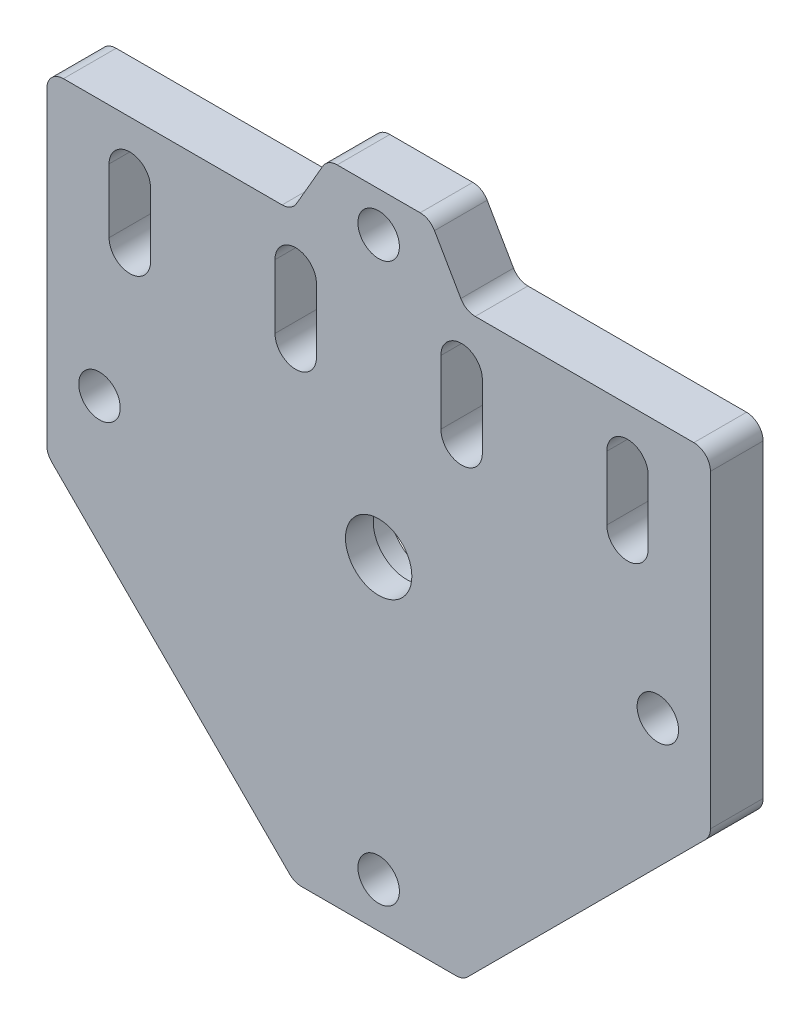
SolidWorks part; units mm, degrees
ref_plane "Front Plane" through (0, 0, 0) normal (0, 0, 1) x (1, 0, 0)
ref_plane "Top Plane" through (0, 0, 0) normal (0, 1, 0) x (1, 0, 0)
ref_plane "Right Plane" through (0, 0, 0) normal (1, 0, 0) x (0, 0, -1)
sketch "Sketch1" plane through (0, 0, 0) normal (0, 0, 1) x (1, 0, 0)
  line L0 (-23.6583, -20.95) -> (-30, -20.95) construction
  line L1 (-28, 10) -> (-1.6395, 10)
  line L2 (-30, 8) -> (-30, -29.3216)
  line L3 (0.6784, -60) -> (19.3216, -60)
  line L4 (50, 8) -> (50, -29.3216)
  line L5 (-5.36, 10) -> (5.36, 10) construction
  line L6 (43.6583, -20.95) -> (50, -20.95) construction
  line L7 (10, -20.95) -> (10, 10) construction
  line L8 (-23.6583, -20.95) -> (10, -20.95) construction
  line L9 (10, -54.6083) -> (10, -60) construction
  line L10 (-29.4142, -30.7358) -> (-0.7358, -59.4142)
  line L11 (20.7358, -59.4142) -> (49.4142, -30.7358)
  line L12 (0.0925, 11) -> (3.268, 16.5)
  line L13 (5, 17.5) -> (15, 17.5)
  line L14 (16.7321, 16.5) -> (19.9075, 11)
  line L15 (10, 10) -> (10, 17.5) construction
  line L17 (21.6395, 10) -> (48, 10)
  line L19 (10, -20.95) -> (43.6583, -20.95) construction
  line L20 (-49.855, -30.15) -> (-39.855, -30.15) construction
  line L21 (10, -54.6083) -> (10, -20.95) construction
  circle A0 centre (10, -20.95) radius 4
  circle A1 centre (43.6583, -20.95) radius 2.5
  circle A2 centre (10, -54.6083) radius 2.5
  circle A3 centre (-23.6583, -20.95) radius 2.5
  arc A4 (50, 8) -> (48, 10) centre (48, 8) ccw
  arc A5 (-28, 10) -> (-30, 8) centre (-28, 8) ccw
  circle A6 centre (10, 12.7083) radius 2.5
  arc A7 (-1.6395, 10) -> (0.0925, 11) centre (-1.6395, 12) ccw
  arc A8 (19.9075, 11) -> (21.6395, 10) centre (21.6395, 12) ccw
  arc A9 (16.7321, 16.5) -> (15, 17.5) centre (15, 15.5) ccw
  arc A10 (5, 17.5) -> (3.268, 16.5) centre (5, 15.5) ccw
  arc A11 (49.4142, -30.7358) -> (50, -29.3216) centre (48, -29.3216) ccw
  arc A12 (20.7358, -59.4142) -> (19.3216, -60) centre (19.3216, -58) cw
  arc A13 (-0.7358, -59.4142) -> (0.6784, -60) centre (0.6784, -58) ccw
  arc A14 (-30, -29.3216) -> (-29.4142, -30.7358) centre (-28, -29.3216) ccw
  point P36 (20.4848, 10)
  point P52 (-30, -30.15)
  dimension "D1" = 8
  dimension "D5" = 5
  dimension "D10" = 6.3417
  dimension "D7" = 2
  dimension "D13" = 2
  dimension "D15" = 2
  dimension "D2" = 70
  dimension "D3" = 30.95
  dimension "D4" = 135
  dimension "D6" = 80
  dimension "D8" = 120
  dimension "D9" = 5.3917
  dimension "D11" = 120
  dimension "D12" = 7.5
  dimension "D14" = 10
extrude "Boss-Extrude1" add sketch "Sketch1" along normal blind 6.35
hole_wizard "Ø5.0mm Dowel Slot1" positions "Sketch4" profile "Sketch3" size "Ø5.0" standard "ANSI Metric" slot yes
sketch "Sketch4" plane through (0, 0, 6.35) normal (0, 0, 1) x (1, 0, 0)
  line L0 (40, -6.35) -> (40, 6.35) construction
  line L4 (-20, 0) -> (0, 0) construction
  line L5 (0, 0) -> (20, 0) construction
  line L6 (20, 0) -> (40, 0) construction
  line L9 (-1.6395, 10) -> (-28, 10) construction
  line L10 (10, -20.95) -> (10, 0) construction
  point P0 (40, 0)
  point P4 (0, 0)
  point P6 (-20, 0)
  point P27 (20, 0)
  dimension "D1" = 12.7
  dimension "D2" = 10
  dimension "D3" = 20
sketch "Sketch3" plane through (40, 0, 6.35) normal (1, 0, 0) x (0, -1, 0)
  line L0 (0, 0) -> (0, 11.5022)
  line L1 (0, 11.5022) -> (2.5, 10)
  line L2 (2.5, 10) -> (2.5, 0)
  line L5 (2.5, 0) -> (0, 0)
  line L10 (0, 11.5022) -> (-2.5, 10) construction
  line L11 (0, -6.35) -> (0, 107.95) construction
  dimension "Hole Dia." = 5
  dimension "Hole Depth" = 10
  dimension "Drill Angle" = 118
sketch "Sketch5" plane through (0, 0, 0) normal (0, 0, -1) x (-1, 0, 0)
  circle A0 centre (-10, -20.95) radius 5.25
  circle A1 centre (-10, -20.95) radius 4 construction
  dimension "D1" = 10.5
extrude "Cut-Extrude1" cut sketch "Sketch5" against normal blind 3
